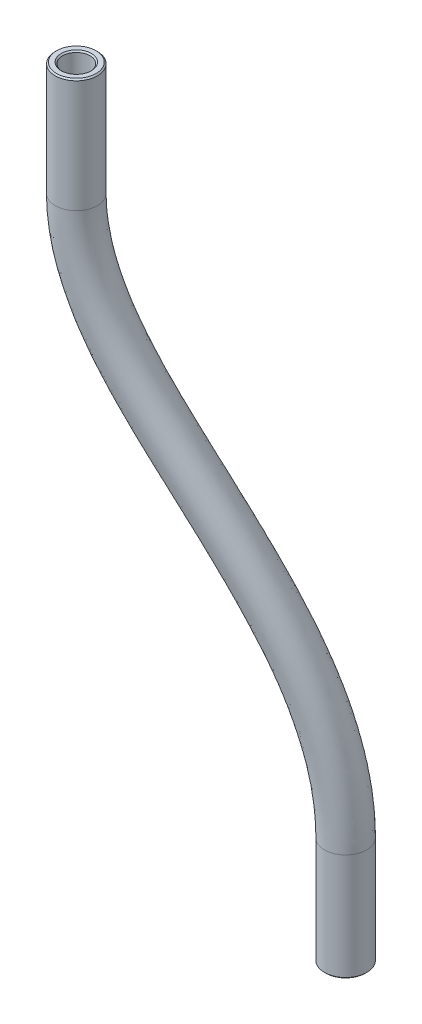
SolidWorks part; units mm, degrees
ref_plane "Front Plane" through (0, 0, 0) normal (0, 0, 1) x (1, 0, 0)
ref_plane "Top Plane" through (0, 0, 0) normal (0, 1, 0) x (1, 0, 0)
ref_plane "Right Plane" through (0, 0, 0) normal (1, 0, 0) x (0, 0, -1)
sketch3d "3DSketch1"
  line L0 (-169.1111, -35.8, -27.0017) -> (-169.1111, -46.6, -27.0017)
  line L1 (-150.0853, -93.2823, -33.525) -> (-150.0853, -103.4823, -33.525)
  spline S0 degree 3 poles (-169.1111, -46.6, -27.0017) (-169.1111, -53.8888, -27.0017) (-159.5982, -68.8838, -30.2634) (-150.0853, -83.2944, -33.525) (-150.0853, -93.2823, -33.525) knots 0 0 0 0 0.430179 1 1 1 1
sketch "Sketch1" plane through (0, -95.3823, 0) normal (0, 1, 0) x (1, 0, 0)
  circle A0 centre (-150.0853, 33.525) radius 1.3
  circle A1 centre (-150.0853, 33.525) radius 2
  circle A2 centre (-150.0853, 33.525) radius 2 construction
  dimension "D1" = 4
  dimension "D2" = 2.6
sweep "Sweep1" add profiles "Sketch1" path "3DSketch1"
chamfer "Chamfer1" distance 0.127 angle 45 4 edges at (-152.0853, -103.4823, -33.525) (-151.3853, -103.4823, -33.525) (-171.1111, -35.8, -27.0017) (-170.4111, -35.8, -27.0017)
